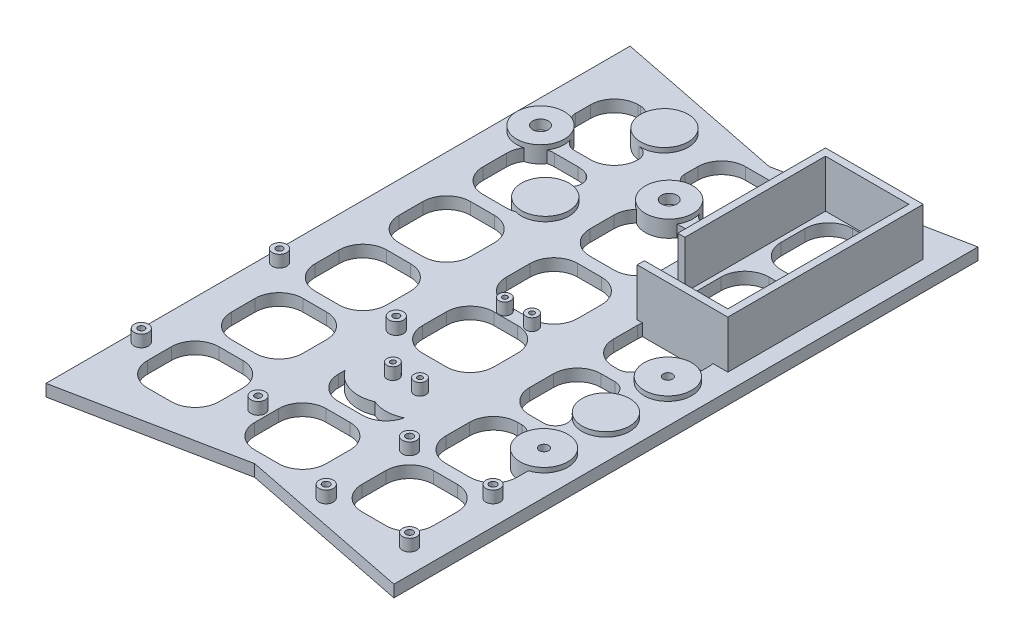
SolidWorks part; units mm, degrees
material "ABS"
ref_plane "Front Plane" through (0, 0, 0) normal (0, 0, 1) x (1, 0, 0)
ref_plane "Top Plane" through (0, 0, 0) normal (0, 1, 0) x (1, 0, 0)
ref_plane "Right Plane" through (0, 0, 0) normal (1, 0, 0) x (0, 0, -1)
ref_axis "X" through (-88.99, 0, 0) along (1, 0, 0)
ref_axis "Y" through (0, 55, 0) along (0, -1, 0)
ref_axis "Z" through (0, 0, -88.99) along (0, 0, 1)
sketch "Sketch1" plane through (0, 0, 0) normal (0, 1, 0) x (1, 0, 0)
  line L0 (-75, 125) -> (0, 110) construction
  line L1 (-75, 125) -> (75, 125) construction
  line L2 (-75, 125) -> (-75, -125) construction
  line L3 (-75, -125) -> (75, -125) construction
  line L4 (75, 125) -> (75, -125) construction
  line L5 (-75, 125) -> (75, -125) construction
  line L6 (-75, -125) -> (75, 125) construction
  line L7 (0, 110) -> (75, 125) construction
  line L8 (-75, 0) -> (75, 0) construction
  line L9 (-75, -125) -> (0, -110) construction
  line L10 (0, -110) -> (75, -125) construction
  line L11 (-73, 122.5604) -> (-73, -122.5604)
  line L12 (-73, -122.5604) -> (0, -107.9604)
  line L13 (0, -107.9604) -> (73, -122.5604)
  line L14 (73, 122.5604) -> (73, -122.5604)
  line L15 (0, 107.9604) -> (73, 122.5604)
  line L16 (-73, 122.5604) -> (0, 107.9604)
  point P0 (0, 0)
  dimension "D1" = 250
  dimension "D2" = 150
  dimension "D3" = 15
  dimension "D4" = 2
extrude "Boss-Extrude1" add sketch "Sketch1" along normal blind 2
sketch "Sketch2" plane through (0, 2, 0) normal (0, 1, 0) x (1, 0, 0)
  line L0 (-73, 122.5604) -> (-73, -122.5604) construction
  line L1 (-50, -102.9604) -> (-40, -102.9604)
  line L2 (-60, -92.9604) -> (-60, -82.9604)
  line L3 (-50, -72.9604) -> (-40, -72.9604)
  line L4 (-30, -92.9604) -> (-30, -82.9604)
  line L5 (-15, -92.9604) -> (-15, -82.9604)
  line L6 (-5, -102.9604) -> (5, -102.9604)
  line L7 (15, -92.9604) -> (15, -82.9604)
  line L8 (-5, -72.9604) -> (5, -72.9604)
  line L9 (30, -92.9604) -> (30, -82.9604)
  line L10 (40, -102.9604) -> (50, -102.9604)
  line L11 (60, -92.9604) -> (60, -82.9604)
  line L12 (40, -72.9604) -> (50, -72.9604)
  line L73 (-60, -57.7762) -> (-60, -47.7762)
  line L74 (-50, -67.7762) -> (-40, -67.7762)
  line L75 (-30, -57.7762) -> (-30, -47.7762)
  line L76 (-50, -37.7762) -> (-40, -37.7762)
  line L77 (-15, -57.7762) -> (-15, -47.7762)
  line L78 (-5, -37.7762) -> (5, -37.7762)
  line L79 (15, -57.7762) -> (15, -47.7762)
  line L80 (-5, -67.7762) -> (5, -67.7762)
  line L81 (30, -57.7762) -> (30, -47.7762)
  line L82 (40, -37.7762) -> (50, -37.7762)
  line L83 (60, -57.7762) -> (60, -47.7762)
  line L84 (40, -67.7762) -> (50, -67.7762)
  line L85 (-60, -22.5921) -> (-60, -12.5921)
  line L86 (-50, -32.5921) -> (-40, -32.5921)
  line L87 (-30, -22.5921) -> (-30, -12.5921)
  line L88 (-50, -2.5921) -> (-40, -2.5921)
  line L89 (-15, -22.5921) -> (-15, -12.5921)
  line L90 (-5, -2.5921) -> (5, -2.5921)
  line L91 (15, -22.5921) -> (15, -12.5921)
  line L92 (-5, -32.5921) -> (5, -32.5921)
  line L93 (30, -22.5921) -> (30, -12.5921)
  line L94 (40, -2.5921) -> (50, -2.5921)
  line L95 (60, -22.5921) -> (60, -12.5921)
  line L96 (40, -32.5921) -> (50, -32.5921)
  line L97 (-60, 12.5921) -> (-60, 22.5921)
  line L98 (-50, 2.5921) -> (-40, 2.5921)
  line L99 (-30, 12.5921) -> (-30, 22.5921)
  line L100 (-50, 32.5921) -> (-40, 32.5921)
  line L101 (-15, 12.5921) -> (-15, 22.5921)
  line L102 (-5, 32.5921) -> (5, 32.5921)
  line L103 (15, 12.5921) -> (15, 22.5921)
  line L104 (-5, 2.5921) -> (5, 2.5921)
  line L105 (30, 12.5921) -> (30, 22.5921)
  line L106 (40, 32.5921) -> (50, 32.5921)
  line L107 (60, 12.5921) -> (60, 22.5921)
  line L108 (40, 2.5921) -> (50, 2.5921)
  line L109 (-60, 47.7762) -> (-60, 57.7762)
  line L110 (-50, 37.7762) -> (-40, 37.7762)
  line L111 (-30, 47.7762) -> (-30, 57.7762)
  line L112 (-50, 67.7762) -> (-40, 67.7762)
  line L113 (-15, 47.7762) -> (-15, 57.7762)
  line L114 (-5, 67.7762) -> (5, 67.7762)
  line L115 (15, 47.7762) -> (15, 57.7762)
  line L116 (-5, 37.7762) -> (5, 37.7762)
  line L117 (30, 47.7762) -> (30, 57.7762)
  line L118 (40, 67.7762) -> (50, 67.7762)
  line L119 (60, 47.7762) -> (60, 57.7762)
  line L120 (40, 37.7762) -> (50, 37.7762)
  line L121 (-60, 82.9604) -> (-60, 92.9604)
  line L122 (-50, 72.9604) -> (-40, 72.9604)
  line L123 (-30, 82.9604) -> (-30, 92.9604)
  line L124 (-50, 102.9604) -> (-40, 102.9604)
  line L125 (-15, 82.9604) -> (-15, 92.9604)
  line L126 (-5, 102.9604) -> (5, 102.9604)
  line L127 (15, 82.9604) -> (15, 92.9604)
  line L128 (-5, 72.9604) -> (5, 72.9604)
  line L129 (30, 82.9604) -> (30, 92.9604)
  line L130 (40, 102.9604) -> (50, 102.9604)
  line L131 (60, 82.9604) -> (60, 92.9604)
  line L132 (40, 72.9604) -> (50, 72.9604)
  arc A0 (-60, -92.9604) -> (-50, -102.9604) centre (-50, -92.9604) ccw
  arc A1 (-40, -102.9604) -> (-30, -92.9604) centre (-40, -92.9604) ccw
  arc A2 (-30, -82.9604) -> (-40, -72.9604) centre (-40, -82.9604) ccw
  arc A3 (-50, -72.9604) -> (-60, -82.9604) centre (-50, -82.9604) ccw
  arc A4 (60, -82.9604) -> (50, -72.9604) centre (50, -82.9604) ccw
  arc A5 (50, -102.9604) -> (60, -92.9604) centre (50, -92.9604) ccw
  arc A6 (40, -102.9604) -> (30, -92.9604) centre (40, -92.9604) cw
  arc A7 (30, -82.9604) -> (40, -72.9604) centre (40, -82.9604) cw
  arc A8 (-15, -82.9604) -> (-5, -72.9604) centre (-5, -82.9604) cw
  arc A9 (-15, -92.9604) -> (-5, -102.9604) centre (-5, -92.9604) ccw
  arc A10 (15, -92.9604) -> (5, -102.9604) centre (5, -92.9604) cw
  arc A11 (15, -82.9604) -> (5, -72.9604) centre (5, -82.9604) ccw
  arc A12 (-50, -37.7762) -> (-60, -47.7762) centre (-50, -47.7762) ccw
  arc A13 (-60, -57.7762) -> (-50, -67.7762) centre (-50, -57.7762) ccw
  arc A14 (-40, -67.7762) -> (-30, -57.7762) centre (-40, -57.7762) ccw
  arc A15 (-30, -47.7762) -> (-40, -37.7762) centre (-40, -47.7762) ccw
  arc A16 (-15, -57.7762) -> (-5, -67.7762) centre (-5, -57.7762) ccw
  arc A17 (-15, -47.7762) -> (-5, -37.7762) centre (-5, -47.7762) cw
  arc A18 (15, -47.7762) -> (5, -37.7762) centre (5, -47.7762) ccw
  arc A19 (15, -57.7762) -> (5, -67.7762) centre (5, -57.7762) cw
  arc A20 (30, -47.7762) -> (40, -37.7762) centre (40, -47.7762) cw
  arc A21 (40, -67.7762) -> (30, -57.7762) centre (40, -57.7762) cw
  arc A22 (60, -47.7762) -> (50, -37.7762) centre (50, -47.7762) ccw
  arc A23 (50, -67.7762) -> (60, -57.7762) centre (50, -57.7762) ccw
  arc A24 (-50, -2.5921) -> (-60, -12.5921) centre (-50, -12.5921) ccw
  arc A25 (-60, -22.5921) -> (-50, -32.5921) centre (-50, -22.5921) ccw
  arc A26 (-40, -32.5921) -> (-30, -22.5921) centre (-40, -22.5921) ccw
  arc A27 (-30, -12.5921) -> (-40, -2.5921) centre (-40, -12.5921) ccw
  arc A28 (-15, -22.5921) -> (-5, -32.5921) centre (-5, -22.5921) ccw
  arc A29 (-15, -12.5921) -> (-5, -2.5921) centre (-5, -12.5921) cw
  arc A30 (15, -12.5921) -> (5, -2.5921) centre (5, -12.5921) ccw
  arc A31 (15, -22.5921) -> (5, -32.5921) centre (5, -22.5921) cw
  arc A32 (30, -12.5921) -> (40, -2.5921) centre (40, -12.5921) cw
  arc A33 (40, -32.5921) -> (30, -22.5921) centre (40, -22.5921) cw
  arc A34 (60, -12.5921) -> (50, -2.5921) centre (50, -12.5921) ccw
  arc A35 (50, -32.5921) -> (60, -22.5921) centre (50, -22.5921) ccw
  arc A36 (-50, 32.5921) -> (-60, 22.5921) centre (-50, 22.5921) ccw
  arc A37 (-60, 12.5921) -> (-50, 2.5921) centre (-50, 12.5921) ccw
  arc A38 (-40, 2.5921) -> (-30, 12.5921) centre (-40, 12.5921) ccw
  arc A39 (-30, 22.5921) -> (-40, 32.5921) centre (-40, 22.5921) ccw
  arc A40 (-15, 12.5921) -> (-5, 2.5921) centre (-5, 12.5921) ccw
  arc A41 (-15, 22.5921) -> (-5, 32.5921) centre (-5, 22.5921) cw
  arc A42 (15, 22.5921) -> (5, 32.5921) centre (5, 22.5921) ccw
  arc A43 (15, 12.5921) -> (5, 2.5921) centre (5, 12.5921) cw
  arc A44 (30, 22.5921) -> (40, 32.5921) centre (40, 22.5921) cw
  arc A45 (40, 2.5921) -> (30, 12.5921) centre (40, 12.5921) cw
  arc A46 (60, 22.5921) -> (50, 32.5921) centre (50, 22.5921) ccw
  arc A47 (50, 2.5921) -> (60, 12.5921) centre (50, 12.5921) ccw
  arc A48 (-50, 67.7762) -> (-60, 57.7762) centre (-50, 57.7762) ccw
  arc A49 (-60, 47.7762) -> (-50, 37.7762) centre (-50, 47.7762) ccw
  arc A50 (-40, 37.7762) -> (-30, 47.7762) centre (-40, 47.7762) ccw
  arc A51 (-30, 57.7762) -> (-40, 67.7762) centre (-40, 57.7762) ccw
  arc A52 (-15, 47.7762) -> (-5, 37.7762) centre (-5, 47.7762) ccw
  arc A53 (-15, 57.7762) -> (-5, 67.7762) centre (-5, 57.7762) cw
  arc A54 (15, 57.7762) -> (5, 67.7762) centre (5, 57.7762) ccw
  arc A55 (15, 47.7762) -> (5, 37.7762) centre (5, 47.7762) cw
  arc A56 (30, 57.7762) -> (40, 67.7762) centre (40, 57.7762) cw
  arc A57 (40, 37.7762) -> (30, 47.7762) centre (40, 47.7762) cw
  arc A58 (60, 57.7762) -> (50, 67.7762) centre (50, 57.7762) ccw
  arc A59 (50, 37.7762) -> (60, 47.7762) centre (50, 47.7762) ccw
  arc A60 (-50, 102.9604) -> (-60, 92.9604) centre (-50, 92.9604) ccw
  arc A61 (-60, 82.9604) -> (-50, 72.9604) centre (-50, 82.9604) ccw
  arc A62 (-40, 72.9604) -> (-30, 82.9604) centre (-40, 82.9604) ccw
  arc A63 (-30, 92.9604) -> (-40, 102.9604) centre (-40, 92.9604) ccw
  arc A64 (-15, 82.9604) -> (-5, 72.9604) centre (-5, 82.9604) ccw
  arc A65 (-15, 92.9604) -> (-5, 102.9604) centre (-5, 92.9604) cw
  arc A66 (15, 92.9604) -> (5, 102.9604) centre (5, 92.9604) ccw
  arc A67 (15, 82.9604) -> (5, 72.9604) centre (5, 82.9604) cw
  arc A68 (30, 92.9604) -> (40, 102.9604) centre (40, 92.9604) cw
  arc A69 (40, 72.9604) -> (30, 82.9604) centre (40, 82.9604) cw
  arc A70 (60, 92.9604) -> (50, 102.9604) centre (50, 92.9604) ccw
  arc A71 (50, 72.9604) -> (60, 82.9604) centre (50, 82.9604) ccw
  point P81 (-30, -102.9604)
  point P84 (-30, -72.9604)
  point P87 (-60, -72.9604)
  dimension "D9" = 10
  dimension "D7" = 10
  dimension "D1" = 30
  dimension "D2" = 30
  dimension "D3" = 13
  dimension "D4" = 5
  dimension "D6" = 15
  dimension "D8" = 6
  dimension "D10" = 5
  dimension "D5" = 3
extrude "Cut-Extrude1" cut sketch "Sketch2" against normal through all
sketch "Sketch3" plane through (0, 2, 0) normal (0, 1, 0) x (1, 0, 0)
  line L1 (-73, 122.5604) -> (-73, -122.5604) construction
  circle A0 centre (-68, -29.5604) radius 3
  circle A1 centre (-19, -29.5604) radius 3
  circle A2 centre (-68, -87.5604) radius 3
  circle A3 centre (-19, -87.5604) radius 3
  dimension "D1" = 6
  dimension "D2" = 49
  dimension "D3" = 58
  dimension "D4" = 5
  dimension "D5" = 35
extrude "Boss-Extrude2" add sketch "Sketch3" along normal blind 5 and the other way through all
sketch "Sketch4" plane through (0, 7, 0) normal (0, 1, 0) x (1, 0, 0)
  circle A1 centre (-19, -87.5604) radius 1.35
  circle A2 centre (-68, -87.5604) radius 1.35
  circle A3 centre (-68, -29.5604) radius 1.35
  circle A4 centre (-19, -29.5604) radius 1.35
  dimension "D1" = 2.7
extrude "Cut-Extrude2" cut sketch "Sketch4" against normal through all
sketch "Sketch5" plane through (0, 2, 0) normal (0, 1, 0) x (1, 0, 0)
  line L0 (30, -87.9604) -> (60, -87.9604) construction
  line L1 (30, -82.9604) -> (30, -92.9604) construction
  line L2 (60, -92.9604) -> (60, -82.9604) construction
  circle A0 centre (27.5, -70.4604) radius 3
  circle A2 centre (62.5, -70.4604) radius 3
  circle A4 centre (62.5, -105.4604) radius 3
  circle A6 centre (27.5, -105.4604) radius 3
  circle A9 centre (45, -87.9604) radius 24.7487 construction
  dimension "D2" = 6
  dimension "D3" = 35
  dimension "D4" = 35
extrude "Boss-Extrude3" add sketch "Sketch5" along normal blind 5
sketch "Sketch6" plane through (0, 7, 0) normal (0, 1, 0) x (1, 0, 0)
  circle A0 centre (27.5, -70.4604) radius 1.5
  circle A1 centre (62.5, -70.4604) radius 1.5
  circle A2 centre (62.5, -105.4604) radius 1.5
  circle A3 centre (27.5, -105.4604) radius 1.5
  dimension "D1" = 3
extrude "Cut-Extrude3" cut sketch "Sketch6" against normal through all
sketch "Sketch7" plane through (0, 2, 0) normal (0, 1, 0) x (1, 0, 0)
  line L0 (73, -122.5604) -> (73, 122.5604) construction
  line L1 (30, -17.5921) -> (73, -17.5921) construction
  line L2 (30, -12.5921) -> (30, -22.5921) construction
  line L3 (57, 8.4079) -> (57, -43.5921) construction
  circle A0 centre (57, -43.5921) radius 10
  circle A1 centre (57, 8.4079) radius 10
  circle A2 centre (57, -17.5921) radius 10
  point P6 (51.5, -17.5921)
  point P13 (57, -17.5921)
  dimension "D1" = 20
  dimension "D2" = 16
  dimension "D3" = 52
extrude "Boss-Extrude4" add sketch "Sketch7" along normal blind 2 and the other way through all
sketch "Sketch8" plane through (0, 4, 0) normal (0, 1, 0) x (1, 0, 0)
  circle A0 centre (57, 8.4079) radius 1.95
  circle A1 centre (57, -43.5921) radius 1.95
  dimension "D1" = 3.9
extrude "Cut-Extrude4" cut sketch "Sketch8" against normal through all
sketch "Sketch9" plane through (0, 2, 0) normal (0, 1, 0) x (1, 0, 0)
  line L0 (73, 0) -> (-73, 0) construction
  line L1 (73, -122.5604) -> (73, 122.5604) construction
  line L2 (-73, 122.5604) -> (-73, -122.5604) construction
  circle A0 centre (-3, 0) radius 2.5
  circle A1 centre (-3, -47) radius 2.5
  circle A2 centre (8.4, -47) radius 2.5
  circle A3 centre (8.4, 0) radius 2.5
  dimension "D1" = 5
  dimension "D4" = 70
  dimension "D2" = 11.4
  dimension "D3" = 47
extrude "Boss-Extrude5" add sketch "Sketch9" along normal blind 5
sketch "Sketch16" plane through (0, 2, 0) normal (0, -1, 0) x (1, 0, 0)
  line L0 (-5, 32.5921) -> (5, 32.5921) construction
  circle A0 centre (8.4, 47) radius 14.4079
  circle A1 centre (-3, 47) radius 14.4079
  circle M3 centre (8.4, 47) radius 2.5
extrude "Boss-Extrude10" add sketch "Sketch16" along normal up to surface (2 mm away) contours A0 A1 | A0 A1 M3 | M3 | A1 A0 region at (14.3268, 2, 47) region at (2.3422, 2, 47) region at (-8.9268, 2, 47) region at (8.4, 2, 47) up to face at (57, 0, -6.4579)
sketch "Sketch10" plane through (0, 7, 0) normal (0, 1, 0) x (1, 0, 0)
  circle A0 centre (8.4, 0) radius 1.05
  circle A1 centre (8.4, -47) radius 1.05
  circle A2 centre (-3, -47) radius 1.05
  circle A3 centre (-3, 0) radius 1.05
  dimension "D1" = 2.1
extrude "Cut-Extrude5" cut sketch "Sketch10" against normal through all
sketch "Sketch11" plane through (0, 2, 0) normal (0, 1, 0) x (1, 0, 0)
  line L0 (-73, 122.5604) -> (-73, -122.5604) construction
  line L1 (-34, 97.9604) -> (-34, 47.9604) construction
  line L2 (-61, 72.9604) -> (-7, 72.9604) construction
  circle A3 centre (-7, 72.9604) radius 10
  circle A4 centre (-61, 72.9604) radius 10
  circle A5 centre (-34, 97.9604) radius 10
  circle A6 centre (-34, 47.9604) radius 10
  point P11 (-34, 72.9604)
  dimension "D1" = 20
  dimension "D2" = 54
  dimension "D3" = 35
  dimension "D4" = 12
  dimension "D5" = 50
extrude "Boss-Extrude6" add sketch "Sketch11" along normal blind 2 and the other way through all
sketch "Sketch12" plane through (0, 4, 0) normal (0, 1, 0) x (1, 0, 0)
  circle A0 centre (-61, 72.9604) radius 3.25
  circle A1 centre (-7, 72.9604) radius 3.25
  dimension "D1" = 6.5
extrude "Cut-Extrude6" cut sketch "Sketch12" against normal through all
sketch "Sketch13" plane through (0, 2, 0) normal (0, 1, 0) x (1, 0, 0)
  line L0 (28, 24.5604) -> (66, 24.5604)
  line L1 (66, 24.5604) -> (66, 106.5604)
  line L2 (66, 106.5604) -> (25, 106.5604)
  line L3 (25, 106.5604) -> (25, 44.5604)
  line L4 (25, 44.5604) -> (28, 44.5604)
  line L5 (28, 44.5604) -> (28, 103.5604)
  line L6 (28, 103.5604) -> (63, 103.5604)
  line L7 (63, 103.5604) -> (63, 27.5604)
  line L8 (63, 27.5604) -> (28, 27.5604)
  line L9 (28, 27.5604) -> (28, 24.5604)
  line L10 (73, -122.5604) -> (73, 122.5604) construction
  dimension "D1" = 62
  dimension "D2" = 3
  dimension "D3" = 3
  dimension "D4" = 3
  dimension "D5" = 3
  dimension "D6" = 35
  dimension "D7" = 76
  dimension "D8" = 16
  dimension "D9" = 7
extrude "Boss-Extrude7" add sketch "Sketch13" along normal blind 20 and the other way through all
fillet "Fillet2" radius 5 11 edges at (48.8651, 1, -2.5921) (48.8651, 1, 37.7762) (58.7473, 1, 27.4382) (58.7473, 1, 7.7459) (-30, 1, -57.1255) (-14.4353, 1, -79.6474) (3, 1, -72.9604) (-59.9999, 1, -82.9103) (-51.0001, 1, -73.0105) (-42.6603, 1, -102.9604) (-30, 1, -88.7952)
sketch "Sketch15" plane through (0, 0, 0) normal (0, -1, 0) x (1, 0, 0)
  line L0 (0, 107.9604) -> (73, 122.5604) construction
  line L1 (-73, 122.5604) -> (0, 107.9604) construction
  line L2 (73, 122.5604) -> (73, -122.5604) construction
  line L3 (73, -122.5604) -> (0, -107.9604) construction
  line L4 (0, -107.9604) -> (-73, -122.5604) construction
  line L5 (-73, -122.5604) -> (-73, 122.5604) construction
  line L6 (0, 107.9604) -> (73, 122.5604)
  line L7 (-73, 122.5604) -> (0, 107.9604)
  line L8 (73, 122.5604) -> (73, -122.5604)
  line L9 (73, -122.5604) -> (0, -107.9604)
  line L10 (0, -107.9604) -> (-73, -122.5604)
  line L11 (-73, -122.5604) -> (-73, 122.5604)
  line L12 (0, 104.901) -> (70, 118.901)
  line L13 (70, 118.901) -> (70, -118.901)
  line L14 (70, -118.901) -> (0, -104.901)
  line L15 (0, -104.901) -> (-70, -118.901)
  line L16 (-70, -118.901) -> (-70, 118.901)
  line L17 (-70, 118.901) -> (0, 104.901)
  dimension "D1" = 3
extrude "Boss-Extrude9" add sketch "Sketch15" along normal blind 3
sketch "Sketch17" plane through (0, 0, 0) normal (0, -1, 0) x (1, 0, 0)
  line L4 (-40, 72.9604) -> (-50, 72.9604) construction
  line L5 (-30, 92.9604) -> (-30, 82.9604) construction
  line L6 (-50, 102.9604) -> (-40, 102.9604) construction
  line L7 (-60, 82.9604) -> (-60, 92.9604) construction
  line L8 (-40, 37.7762) -> (-50, 37.7762) construction
  line L9 (-30, 57.7762) -> (-30, 47.7762) construction
  line L10 (-50, 67.7762) -> (-40, 67.7762) construction
  line L11 (-60, 47.7762) -> (-60, 57.7762) construction
  line L12 (-15, 54.9742) -> (-15, 57.7762) construction
  line L13 (-5, 67.7762) -> (5, 67.7762) construction
  line L14 (5, 2.5921) -> (-5, 2.5921) construction
  line L15 (15, 22.5921) -> (15, 12.5921) construction
  line L16 (-5, 32.5921) -> (5, 32.5921) construction
  line L17 (-15, 12.5921) -> (-15, 22.5921) construction
  line L18 (-60, 12.5921) -> (-60, 22.5921) construction
  line L19 (-40, 2.5921) -> (-50, 2.5921) construction
  line L20 (-30, 22.5921) -> (-30, 12.5921) construction
  line L21 (-50, 32.5921) -> (-40, 32.5921) construction
  line L94 (-40, 72.9604) -> (-50, 72.9604)
  line L95 (-30, 92.9604) -> (-30, 82.9604)
  line L96 (-50, 102.9604) -> (-40, 102.9604)
  line L97 (-60, 82.9604) -> (-60, 92.9604)
  line L98 (-40, 37.7762) -> (-50, 37.7762)
  line L99 (-30, 57.7762) -> (-30, 47.7762)
  line L100 (-50, 67.7762) -> (-40, 67.7762)
  line L101 (-60, 47.7762) -> (-60, 57.7762)
  line L102 (-15, 54.9742) -> (-15, 57.7762)
  line L103 (-5, 67.7762) -> (5, 67.7762)
  line L104 (5, 2.5921) -> (-5, 2.5921)
  line L105 (15, 22.5921) -> (15, 12.5921)
  line L106 (-5, 32.5921) -> (5, 32.5921)
  line L107 (-15, 12.5921) -> (-15, 22.5921)
  line L108 (-60, 12.5921) -> (-60, 22.5921)
  line L109 (-40, 2.5921) -> (-50, 2.5921)
  line L110 (-30, 22.5921) -> (-30, 12.5921)
  line L111 (-50, 32.5921) -> (-40, 32.5921)
  line L112 (60, 57.7762) -> (60, 53.1315) construction
  line L113 (42.0222, 37.7762) -> (40, 37.7762) construction
  line L114 (30, 47.7762) -> (30, 57.7762) construction
  line L115 (40, 67.7762) -> (50, 67.7762) construction
  line L116 (60, 92.9604) -> (60, 82.9604) construction
  line L117 (50, 72.9604) -> (40, 72.9604) construction
  line L118 (30, 82.9604) -> (30, 92.9604) construction
  line L119 (40, 102.9604) -> (50, 102.9604) construction
  line L120 (5, 72.9604) -> (-5, 72.9604) construction
  line L121 (15, 92.9604) -> (15, 82.9604) construction
  line L122 (-5, 102.9604) -> (5, 102.9604) construction
  line L123 (-15, 82.9604) -> (-15, 92.9604) construction
  line L124 (60, 57.7762) -> (60, 53.1315)
  line L125 (42.0222, 37.7762) -> (40, 37.7762)
  line L126 (30, 47.7762) -> (30, 57.7762)
  line L127 (40, 67.7762) -> (50, 67.7762)
  line L128 (60, 92.9604) -> (60, 82.9604)
  line L129 (50, 72.9604) -> (40, 72.9604)
  line L130 (30, 82.9604) -> (30, 92.9604)
  line L131 (40, 102.9604) -> (50, 102.9604)
  line L132 (5, 72.9604) -> (-5, 72.9604)
  line L133 (15, 92.9604) -> (15, 82.9604)
  line L134 (-5, 102.9604) -> (5, 102.9604)
  line L135 (-15, 82.9604) -> (-15, 92.9604)
  line L136 (40, -2.5921) -> (42.0222, -2.5921) construction
  line L137 (30, -22.5921) -> (30, -12.5921) construction
  line L138 (60, -17.9473) -> (60, -22.5921) construction
  line L139 (30.1956, -24.5604) -> (59.8044, -24.5604) construction
  line L140 (58.6785, -27.5604) -> (31.3215, -27.5604) construction
  line L141 (50, -32.5921) -> (40, -32.5921) construction
  line L142 (40, -2.5921) -> (42.0222, -2.5921)
  line L143 (30, -22.5921) -> (30, -12.5921)
  line L144 (60, -17.9473) -> (60, -22.5921)
  line L145 (30.1956, -24.5604) -> (59.8044, -24.5604)
  line L146 (58.6785, -27.5604) -> (31.3215, -27.5604)
  line L147 (50, -32.5921) -> (40, -32.5921)
  line L148 (5, -32.5921) -> (-5, -32.5921) construction
  line L149 (-5, -2.5921) -> (5, -2.5921) construction
  line L150 (-15, -22.5921) -> (-15, -12.5921) construction
  line L151 (15, -12.5921) -> (15, -22.5921) construction
  line L152 (30, 12.5921) -> (30, 22.5921) construction
  line L153 (45.8197, 2.5921) -> (40, 2.5921) construction
  line L154 (40, 32.5921) -> (45.8197, 32.5921) construction
  line L155 (5, -32.5921) -> (-5, -32.5921)
  line L156 (-5, -2.5921) -> (5, -2.5921)
  line L157 (-15, -22.5921) -> (-15, -12.5921)
  line L158 (15, -12.5921) -> (15, -22.5921)
  line L159 (30, 12.5921) -> (30, 22.5921)
  line L160 (45.8197, 2.5921) -> (40, 2.5921)
  line L161 (40, 32.5921) -> (45.8197, 32.5921)
  line L162 (-60, -57.7762) -> (-60, -47.7762) construction
  line L163 (-40, -67.7762) -> (-50, -67.7762) construction
  line L164 (-50, -37.7762) -> (-40, -37.7762) construction
  line L165 (-40, -32.5921) -> (-50, -32.5921) construction
  line L166 (-30, -12.5921) -> (-30, -22.5921) construction
  line L167 (-50, -2.5921) -> (-40, -2.5921) construction
  line L168 (-60, -22.5921) -> (-60, -12.5921) construction
  line L169 (-60, -57.7762) -> (-60, -47.7762)
  line L170 (-40, -67.7762) -> (-50, -67.7762)
  line L171 (-50, -37.7762) -> (-40, -37.7762)
  line L172 (-40, -32.5921) -> (-50, -32.5921)
  line L173 (-30, -12.5921) -> (-30, -22.5921)
  line L174 (-50, -2.5921) -> (-40, -2.5921)
  line L175 (-60, -22.5921) -> (-60, -12.5921)
  line L176 (60, -82.9604) -> (60, -92.9604) construction
  line L177 (50, -102.9604) -> (40, -102.9604) construction
  line L178 (40, -72.9604) -> (50, -72.9604) construction
  line L179 (30, -92.9604) -> (30, -82.9604) construction
  line L180 (15, -82.9604) -> (15, -92.9604) construction
  line L181 (5, -102.9604) -> (-5, -102.9604) construction
  line L182 (-15, -92.9604) -> (-15, -87.6573) construction
  line L186 (60, -82.9604) -> (60, -92.9604)
  line L187 (50, -102.9604) -> (40, -102.9604)
  line L188 (40, -72.9604) -> (50, -72.9604)
  line L189 (30, -92.9604) -> (30, -82.9604)
  line L190 (15, -82.9604) -> (15, -92.9604)
  line L191 (5, -102.9604) -> (-5, -102.9604)
  line L192 (-15, -92.9604) -> (-15, -87.6573)
  line L196 (50, -67.7762) -> (40, -67.7762) construction
  line L197 (60, -47.7762) -> (60, -57.7762) construction
  line L198 (40, -37.7762) -> (50, -37.7762) construction
  line L199 (30, -57.7762) -> (30, -47.7762) construction
  line L200 (5, -67.7762) -> (1.5513, -67.7762) construction
  line L201 (15, -47.7762) -> (15, -57.7762) construction
  line L202 (-5, -37.7762) -> (5, -37.7762) construction
  line L203 (-15, -57.7762) -> (-15, -47.7762) construction
  line L204 (50, -67.7762) -> (40, -67.7762)
  line L205 (60, -47.7762) -> (60, -57.7762)
  line L206 (40, -37.7762) -> (50, -37.7762)
  line L207 (30, -57.7762) -> (30, -47.7762)
  line L208 (5, -67.7762) -> (1.5513, -67.7762)
  line L209 (15, -47.7762) -> (15, -57.7762)
  line L210 (-5, -37.7762) -> (5, -37.7762)
  line L211 (-15, -57.7762) -> (-15, -47.7762)
  line L212 (-30, -82.9604) -> (-30, -82.9938) construction
  line L213 (-46.8579, -72.9604) -> (-40, -72.9604) construction
  line L214 (-60, -92.9604) -> (-60, -86.7081) construction
  line L215 (-49, -102.9604) -> (-50, -102.9604) construction
  line L216 (-30, -82.9604) -> (-30, -82.9938)
  line L217 (-46.8579, -72.9604) -> (-40, -72.9604)
  line L218 (-60, -92.9604) -> (-60, -86.7081)
  line L219 (-49, -102.9604) -> (-50, -102.9604)
  line L220 (-49, -104.9604) -> (-50, -104.9604)
  line L221 (-62, -92.9604) -> (-62, -86.7081)
  line L222 (-46.8579, -70.9604) -> (-40, -70.9604)
  line L223 (-28, -82.9604) -> (-28, -82.9938)
  line L224 (-62, -57.7762) -> (-62, -47.7762)
  line L225 (-40, -69.7762) -> (-50, -69.7762)
  line L226 (-50, -35.7762) -> (-40, -35.7762)
  line L227 (5, -69.7762) -> (0.339, -69.7762)
  line L228 (-17, -57.7762) -> (-17, -47.7762)
  line L229 (-5, -35.7762) -> (5, -35.7762)
  line L230 (17, -47.7762) -> (17, -57.7762)
  line L231 (17, -82.9604) -> (17, -92.9604)
  line L232 (-17, -92.9604) -> (-17, -87.6573)
  line L233 (5, -104.9604) -> (-5, -104.9604)
  line L234 (40, -70.9604) -> (50, -70.9604)
  line L235 (28, -92.9604) -> (28, -82.9604)
  line L236 (50, -104.9604) -> (40, -104.9604)
  line L237 (62, -82.9604) -> (62, -92.9604)
  line L238 (50, -69.7762) -> (40, -69.7762)
  line L239 (28, -57.7762) -> (28, -47.7762)
  line L240 (40, -35.7762) -> (50, -35.7762)
  line L241 (62, -47.7762) -> (62, -57.7762)
  line L242 (40, -0.5921) -> (42.0222, -0.5921)
  line L243 (62, -14.6529) -> (62, -22.5921)
  line L245 (28, -22.5921) -> (28, -12.5921)
  line L247 (50, -34.5921) -> (40, -34.5921)
  line L252 (-40, -34.5921) -> (-50, -34.5921)
  line L253 (-28, -12.5921) -> (-28, -22.5921)
  line L254 (-50, -0.5921) -> (-40, -0.5921)
  line L255 (-62, -22.5921) -> (-62, -12.5921)
  line L256 (-62, 12.5921) -> (-62, 22.5921)
  line L257 (-50, 34.5921) -> (-40, 34.5921)
  line L258 (-28, 22.5921) -> (-28, 12.5921)
  line L259 (-40, 0.5921) -> (-50, 0.5921)
  line L264 (28, 12.5921) -> (28, 22.5921)
  line L265 (40, 34.5921) -> (45.8197, 34.5921)
  line L266 (45.8197, 0.5921) -> (40, 0.5921)
  line L267 (62, 57.7762) -> (62, 49.8371)
  line L268 (42.0222, 35.7762) -> (40, 35.7762)
  line L269 (28, 47.7762) -> (28, 57.7762)
  line L270 (40, 69.7762) -> (50, 69.7762)
  line L271 (-40, 35.7762) -> (-50, 35.7762)
  line L272 (-28, 57.7762) -> (-28, 47.7762)
  line L273 (-50, 69.7762) -> (-40, 69.7762)
  line L274 (-62, 47.7762) -> (-62, 57.7762)
  line L275 (5, 70.9604) -> (-5, 70.9604)
  line L276 (17, 92.9604) -> (17, 82.9604)
  line L277 (-5, 104.9604) -> (5, 104.9604)
  line L278 (-17, 82.9604) -> (-17, 92.9604)
  line L279 (40, 104.9604) -> (50, 104.9604)
  line L280 (28, 82.9604) -> (28, 92.9604)
  line L281 (50, 70.9604) -> (40, 70.9604)
  line L282 (62, 92.9604) -> (62, 82.9604)
  line L283 (-40, 70.9604) -> (-50, 70.9604)
  line L284 (-28, 92.9604) -> (-28, 82.9604)
  line L285 (-50, 104.9604) -> (-40, 104.9604)
  line L286 (-62, 82.9604) -> (-62, 92.9604)
  line L287 (-16, 50.2821) -> (-16, 57.7762)
  line L288 (-5, 68.7762) -> (5, 68.7762)
  line L289 (5, 1.5921) -> (-5, 1.5921)
  line L290 (16, 22.5921) -> (16, 12.5921)
  line L291 (-5, 33.5921) -> (5, 33.5921)
  line L292 (-16, 12.5921) -> (-16, 22.5921)
  line L293 (5, -33.5921) -> (-5, -33.5921)
  line L294 (28.6751, -26.5604) -> (61.3249, -26.5604) construction
  line L295 (61.6271, -25.5604) -> (28.3729, -25.5604) construction
  line L296 (-16, -22.5921) -> (-16, -12.5921)
  line L297 (-5, -1.5921) -> (5, -1.5921)
  line L298 (16, -12.5921) -> (16, -22.5921)
  arc A2 (-60, 82.9604) -> (-50, 72.9604) centre (-50, 82.9604) ccw construction
  arc A3 (-40, 72.9604) -> (-30, 82.9604) centre (-40, 82.9604) ccw construction
  arc A4 (-30, 92.9604) -> (-40, 102.9604) centre (-40, 92.9604) ccw construction
  arc A5 (-50, 102.9604) -> (-60, 92.9604) centre (-50, 92.9604) ccw construction
  arc A6 (-60, 47.7762) -> (-50, 37.7762) centre (-50, 47.7762) ccw construction
  arc A7 (-40, 37.7762) -> (-30, 47.7762) centre (-40, 47.7762) ccw construction
  arc A8 (-30, 57.7762) -> (-40, 67.7762) centre (-40, 57.7762) ccw construction
  arc A9 (-50, 67.7762) -> (-60, 57.7762) centre (-50, 57.7762) ccw construction
  arc A10 (2.7, 60.2325) -> (-15, 54.9742) centre (-3, 47) ccw construction
  arc A11 (14.7664, 59.9251) -> (2.7, 60.2325) centre (8.4, 47) ccw construction
  arc A12 (14.7664, 59.9251) -> (5, 67.7762) centre (5, 57.7762) ccw construction
  arc A13 (-5, 67.7762) -> (-15, 57.7762) centre (-5, 57.7762) ccw construction
  arc A14 (-15, 12.5921) -> (-5, 2.5921) centre (-5, 12.5921) ccw construction
  arc A15 (5, 2.5921) -> (15, 12.5921) centre (5, 12.5921) ccw construction
  arc A16 (15, 22.5921) -> (5, 32.5921) centre (5, 22.5921) ccw construction
  arc A17 (-5, 32.5921) -> (-15, 22.5921) centre (-5, 22.5921) ccw construction
  arc A18 (-60, 12.5921) -> (-50, 2.5921) centre (-50, 12.5921) ccw construction
  arc A19 (-40, 2.5921) -> (-30, 12.5921) centre (-40, 12.5921) ccw construction
  arc A20 (-30, 22.5921) -> (-40, 32.5921) centre (-40, 22.5921) ccw construction
  arc A21 (-50, 32.5921) -> (-60, 22.5921) centre (-50, 22.5921) ccw construction
  arc A102 (-60, 82.9604) -> (-50, 72.9604) centre (-50, 82.9604) ccw
  arc A103 (-40, 72.9604) -> (-30, 82.9604) centre (-40, 82.9604) ccw
  arc A104 (-30, 92.9604) -> (-40, 102.9604) centre (-40, 92.9604) ccw
  arc A105 (-50, 102.9604) -> (-60, 92.9604) centre (-50, 92.9604) ccw
  arc A106 (-60, 47.7762) -> (-50, 37.7762) centre (-50, 47.7762) ccw
  arc A107 (-40, 37.7762) -> (-30, 47.7762) centre (-40, 47.7762) ccw
  arc A108 (-30, 57.7762) -> (-40, 67.7762) centre (-40, 57.7762) ccw
  arc A109 (-50, 67.7762) -> (-60, 57.7762) centre (-50, 57.7762) ccw
  arc A110 (2.7, 60.2325) -> (-15, 54.9742) centre (-3, 47) ccw
  arc A111 (14.7664, 59.9251) -> (2.7, 60.2325) centre (8.4, 47) ccw
  arc A112 (14.7664, 59.9251) -> (5, 67.7762) centre (5, 57.7762) ccw
  arc A113 (-5, 67.7762) -> (-15, 57.7762) centre (-5, 57.7762) ccw
  arc A114 (-15, 12.5921) -> (-5, 2.5921) centre (-5, 12.5921) ccw
  arc A115 (5, 2.5921) -> (15, 12.5921) centre (5, 12.5921) ccw
  arc A116 (15, 22.5921) -> (5, 32.5921) centre (5, 22.5921) ccw
  arc A117 (-5, 32.5921) -> (-15, 22.5921) centre (-5, 22.5921) ccw
  arc A118 (-60, 12.5921) -> (-50, 2.5921) centre (-50, 12.5921) ccw
  arc A119 (-40, 2.5921) -> (-30, 12.5921) centre (-40, 12.5921) ccw
  arc A120 (-30, 22.5921) -> (-40, 32.5921) centre (-40, 22.5921) ccw
  arc A121 (-50, 32.5921) -> (-60, 22.5921) centre (-50, 22.5921) ccw
  arc A122 (60, 57.7762) -> (50, 67.7762) centre (50, 57.7762) ccw construction
  arc A123 (60, 53.1315) -> (47.0148, 43.0482) centre (57, 43.5921) ccw construction
  arc A124 (42.0222, 37.7762) -> (47.0148, 43.0482) centre (42.0222, 42.7762) ccw construction
  arc A125 (30, 47.7762) -> (40, 37.7762) centre (40, 47.7762) ccw construction
  arc A126 (40, 67.7762) -> (30, 57.7762) centre (40, 57.7762) ccw construction
  arc A127 (60, 92.9604) -> (50, 102.9604) centre (50, 92.9604) ccw construction
  arc A128 (50, 72.9604) -> (60, 82.9604) centre (50, 82.9604) ccw construction
  arc A129 (30, 82.9604) -> (40, 72.9604) centre (40, 82.9604) ccw construction
  arc A130 (40, 102.9604) -> (30, 92.9604) centre (40, 92.9604) ccw construction
  arc A131 (-15, 82.9604) -> (-5, 72.9604) centre (-5, 82.9604) ccw construction
  arc A132 (5, 72.9604) -> (15, 82.9604) centre (5, 82.9604) ccw construction
  arc A133 (15, 92.9604) -> (5, 102.9604) centre (5, 92.9604) ccw construction
  arc A134 (-5, 102.9604) -> (-15, 92.9604) centre (-5, 92.9604) ccw construction
  arc A135 (60, 57.7762) -> (50, 67.7762) centre (50, 57.7762) ccw
  arc A136 (60, 53.1315) -> (47.0148, 43.0482) centre (57, 43.5921) ccw
  arc A137 (42.0222, 37.7762) -> (47.0148, 43.0482) centre (42.0222, 42.7762) ccw
  arc A138 (30, 47.7762) -> (40, 37.7762) centre (40, 47.7762) ccw
  arc A139 (40, 67.7762) -> (30, 57.7762) centre (40, 57.7762) ccw
  arc A140 (60, 92.9604) -> (50, 102.9604) centre (50, 92.9604) ccw
  arc A141 (50, 72.9604) -> (60, 82.9604) centre (50, 82.9604) ccw
  arc A142 (30, 82.9604) -> (40, 72.9604) centre (40, 82.9604) ccw
  arc A143 (40, 102.9604) -> (30, 92.9604) centre (40, 92.9604) ccw
  arc A144 (-15, 82.9604) -> (-5, 72.9604) centre (-5, 82.9604) ccw
  arc A145 (5, 72.9604) -> (15, 82.9604) centre (5, 82.9604) ccw
  arc A146 (15, 92.9604) -> (5, 102.9604) centre (5, 92.9604) ccw
  arc A147 (-5, 102.9604) -> (-15, 92.9604) centre (-5, 92.9604) ccw
  arc A148 (47.0148, -7.864) -> (42.0222, -2.5921) centre (42.0222, -7.5921) ccw construction
  arc A149 (40, -2.5921) -> (30, -12.5921) centre (40, -12.5921) ccw construction
  arc A150 (30, -22.5921) -> (30.1956, -24.5604) centre (40, -22.5921) ccw construction
  arc A151 (47.0148, -7.864) -> (60, -17.9473) centre (57, -8.4079) ccw construction
  arc A152 (59.8044, -24.5604) -> (60, -22.5921) centre (50, -22.5921) ccw construction
  arc A153 (50, -32.5921) -> (58.6785, -27.5604) centre (50, -22.5921) ccw construction
  arc A154 (31.3215, -27.5604) -> (40, -32.5921) centre (40, -22.5921) ccw construction
  arc A155 (47.0148, -7.864) -> (42.0222, -2.5921) centre (42.0222, -7.5921) ccw
  arc A156 (40, -2.5921) -> (30, -12.5921) centre (40, -12.5921) ccw
  arc A157 (30, -22.5921) -> (30.1956, -24.5604) centre (40, -22.5921) ccw
  arc A158 (47.0148, -7.864) -> (60, -17.9473) centre (57, -8.4079) ccw
  arc A159 (59.8044, -24.5604) -> (60, -22.5921) centre (50, -22.5921) ccw
  arc A160 (50, -32.5921) -> (58.6785, -27.5604) centre (50, -22.5921) ccw
  arc A161 (31.3215, -27.5604) -> (40, -32.5921) centre (40, -22.5921) ccw
  arc A162 (5, -32.5921) -> (15, -22.5921) centre (5, -22.5921) ccw construction
  arc A163 (15, -12.5921) -> (5, -2.5921) centre (5, -12.5921) ccw construction
  arc A164 (-5, -2.5921) -> (-15, -12.5921) centre (-5, -12.5921) ccw construction
  arc A165 (-15, -22.5921) -> (-5, -32.5921) centre (-5, -22.5921) ccw construction
  arc A166 (30, 12.5921) -> (40, 2.5921) centre (40, 12.5921) ccw construction
  arc A167 (45.8197, 2.5921) -> (49.5464, 10.9254) centre (45.8197, 7.5921) ccw construction
  arc A168 (49.5464, 24.2587) -> (49.5464, 10.9254) centre (57, 17.5921) ccw construction
  arc A169 (49.5464, 24.2587) -> (45.8197, 32.5921) centre (45.8197, 27.5921) ccw construction
  arc A170 (40, 32.5921) -> (30, 22.5921) centre (40, 22.5921) ccw construction
  arc A171 (5, -32.5921) -> (15, -22.5921) centre (5, -22.5921) ccw
  arc A172 (15, -12.5921) -> (5, -2.5921) centre (5, -12.5921) ccw
  arc A173 (-5, -2.5921) -> (-15, -12.5921) centre (-5, -12.5921) ccw
  arc A174 (-15, -22.5921) -> (-5, -32.5921) centre (-5, -22.5921) ccw
  arc A175 (30, 12.5921) -> (40, 2.5921) centre (40, 12.5921) ccw
  arc A176 (45.8197, 2.5921) -> (49.5464, 10.9254) centre (45.8197, 7.5921) ccw
  arc A177 (49.5464, 24.2587) -> (49.5464, 10.9254) centre (57, 17.5921) ccw
  arc A178 (49.5464, 24.2587) -> (45.8197, 32.5921) centre (45.8197, 27.5921) ccw
  arc A179 (40, 32.5921) -> (30, 22.5921) centre (40, 22.5921) ccw
  arc A180 (-50, -37.7762) -> (-60, -47.7762) centre (-50, -47.7762) ccw construction
  arc A181 (-60, -57.7762) -> (-58.3182, -63.3267) centre (-50, -57.7762) ccw construction
  arc A182 (-52.6818, -67.4099) -> (-50, -67.7762) centre (-50, -57.7762) ccw construction
  arc A183 (-52.6818, -67.4099) -> (-58.3182, -63.3267) centre (-61, -72.9604) ccw construction
  arc A184 (-40, -67.7762) -> (-36.1656, -67.0119) centre (-40, -57.7762) ccw construction
  arc A185 (-36.1656, -67.0119) -> (-36.7219, -57.5828) centre (-38.0828, -62.3941) ccw construction
  arc A186 (-36.7074, -38.3339) -> (-36.7219, -57.5828) centre (-34, -47.9604) ccw construction
  arc A187 (-36.7074, -38.3339) -> (-40, -37.7762) centre (-40, -47.7762) ccw construction
  arc A188 (-60, -22.5921) -> (-50, -32.5921) centre (-50, -22.5921) ccw construction
  arc A189 (-40, -32.5921) -> (-30, -22.5921) centre (-40, -22.5921) ccw construction
  arc A190 (-30, -12.5921) -> (-40, -2.5921) centre (-40, -12.5921) ccw construction
  arc A191 (-50, -2.5921) -> (-60, -12.5921) centre (-50, -12.5921) ccw construction
  arc A192 (-50, -37.7762) -> (-60, -47.7762) centre (-50, -47.7762) ccw
  arc A193 (-60, -57.7762) -> (-58.3182, -63.3267) centre (-50, -57.7762) ccw
  arc A194 (-52.6818, -67.4099) -> (-50, -67.7762) centre (-50, -57.7762) ccw
  arc A195 (-52.6818, -67.4099) -> (-58.3182, -63.3267) centre (-61, -72.9604) ccw
  arc A196 (-40, -67.7762) -> (-36.1656, -67.0119) centre (-40, -57.7762) ccw
  arc A197 (-36.1656, -67.0119) -> (-36.7219, -57.5828) centre (-38.0828, -62.3941) ccw
  arc A198 (-36.7074, -38.3339) -> (-36.7219, -57.5828) centre (-34, -47.9604) ccw
  arc A199 (-36.7074, -38.3339) -> (-40, -37.7762) centre (-40, -47.7762) ccw
  arc A200 (-60, -22.5921) -> (-50, -32.5921) centre (-50, -22.5921) ccw
  arc A201 (-40, -32.5921) -> (-30, -22.5921) centre (-40, -22.5921) ccw
  arc A202 (-30, -12.5921) -> (-40, -2.5921) centre (-40, -12.5921) ccw
  arc A203 (-50, -2.5921) -> (-60, -12.5921) centre (-50, -12.5921) ccw
  arc A204 (60, -82.9604) -> (50, -72.9604) centre (50, -82.9604) ccw construction
  arc A205 (50, -102.9604) -> (60, -92.9604) centre (50, -92.9604) ccw construction
  arc A206 (40, -72.9604) -> (30, -82.9604) centre (40, -82.9604) ccw construction
  arc A207 (30, -92.9604) -> (40, -102.9604) centre (40, -92.9604) ccw construction
  arc A208 (5, -102.9604) -> (15, -92.9604) centre (5, -92.9604) ccw construction
  arc A209 (15, -82.9604) -> (8.9787, -73.786) centre (5, -82.9604) ccw construction
  arc A210 (8.9787, -73.786) -> (2.3262, -76.5689) centre (6.9893, -78.3732) ccw construction
  arc A211 (-9, -82.7584) -> (2.3262, -76.5689) centre (-7, -72.9604) ccw construction
  arc A212 (-9, -82.7584) -> (-15, -87.6573) centre (-10, -87.6573) ccw construction
  arc A213 (-15, -92.9604) -> (-5, -102.9604) centre (-5, -92.9604) ccw construction
  arc A222 (60, -82.9604) -> (50, -72.9604) centre (50, -82.9604) ccw
  arc A223 (50, -102.9604) -> (60, -92.9604) centre (50, -92.9604) ccw
  arc A224 (40, -72.9604) -> (30, -82.9604) centre (40, -82.9604) ccw
  arc A225 (30, -92.9604) -> (40, -102.9604) centre (40, -92.9604) ccw
  arc A226 (5, -102.9604) -> (15, -92.9604) centre (5, -92.9604) ccw
  arc A227 (15, -82.9604) -> (8.9787, -73.786) centre (5, -82.9604) ccw
  arc A228 (8.9787, -73.786) -> (2.3262, -76.5689) centre (6.9893, -78.3732) ccw
  arc A229 (-9, -82.7584) -> (2.3262, -76.5689) centre (-7, -72.9604) ccw
  arc A230 (-9, -82.7584) -> (-15, -87.6573) centre (-10, -87.6573) ccw
  arc A231 (-15, -92.9604) -> (-5, -102.9604) centre (-5, -92.9604) ccw
  arc A235 (-34.6667, -87.9826) -> (-44, -97.9604) centre (-34, -97.9604) ccw construction
  arc A236 (-34.6667, -87.9826) -> (-30, -82.9938) centre (-35, -82.9938) ccw construction
  arc A240 (50, -67.7762) -> (60, -57.7762) centre (50, -57.7762) ccw construction
  arc A241 (60, -47.7762) -> (50, -37.7762) centre (50, -47.7762) ccw construction
  arc A242 (40, -37.7762) -> (30, -47.7762) centre (40, -47.7762) ccw construction
  arc A243 (30, -57.7762) -> (40, -67.7762) centre (40, -57.7762) ccw construction
  arc A244 (5, -67.7762) -> (15, -57.7762) centre (5, -57.7762) ccw construction
  arc A245 (15, -47.7762) -> (5, -37.7762) centre (5, -47.7762) ccw construction
  arc A246 (-5, -37.7762) -> (-15, -47.7762) centre (-5, -47.7762) ccw construction
  arc A247 (-15, -57.7762) -> (-12.3761, -64.5285) centre (-5, -57.7762) ccw construction
  arc A248 (1.5513, -67.7762) -> (-12.3761, -64.5285) centre (-7, -72.9604) ccw construction
  arc A249 (50, -67.7762) -> (60, -57.7762) centre (50, -57.7762) ccw
  arc A250 (60, -47.7762) -> (50, -37.7762) centre (50, -47.7762) ccw
  arc A251 (40, -37.7762) -> (30, -47.7762) centre (40, -47.7762) ccw
  arc A252 (30, -57.7762) -> (40, -67.7762) centre (40, -57.7762) ccw
  arc A253 (5, -67.7762) -> (15, -57.7762) centre (5, -57.7762) ccw
  arc A254 (15, -47.7762) -> (5, -37.7762) centre (5, -47.7762) ccw
  arc A255 (-5, -37.7762) -> (-15, -47.7762) centre (-5, -47.7762) ccw
  arc A256 (-15, -57.7762) -> (-12.3761, -64.5285) centre (-5, -57.7762) ccw
  arc A257 (1.5513, -67.7762) -> (-12.3761, -64.5285) centre (-7, -72.9604) ccw
  arc A258 (-30, -82.9604) -> (-40, -72.9604) centre (-40, -82.9604) ccw construction
  arc A259 (-46.8579, -72.9604) -> (-51.5719, -76.2937) centre (-46.8579, -77.9604) ccw construction
  arc A260 (-57, -82.1255) -> (-51.5719, -76.2937) centre (-61, -72.9604) ccw construction
  arc A261 (-57, -82.1255) -> (-60, -86.7081) centre (-55, -86.7081) ccw construction
  arc A262 (-60, -92.9604) -> (-50, -102.9604) centre (-50, -92.9604) ccw construction
  arc A263 (-49, -102.9604) -> (-44, -97.9604) centre (-49, -97.9604) ccw construction
  arc A264 (-34.6667, -87.9826) -> (-44, -97.9604) centre (-34, -97.9604) ccw
  arc A265 (-34.6667, -87.9826) -> (-30, -82.9938) centre (-35, -82.9938) ccw
  arc A266 (-30, -82.9604) -> (-40, -72.9604) centre (-40, -82.9604) ccw
  arc A267 (-46.8579, -72.9604) -> (-51.5719, -76.2937) centre (-46.8579, -77.9604) ccw
  arc A268 (-57, -82.1255) -> (-51.5719, -76.2937) centre (-61, -72.9604) ccw
  arc A269 (-57, -82.1255) -> (-60, -86.7081) centre (-55, -86.7081) ccw
  arc A270 (-60, -92.9604) -> (-50, -102.9604) centre (-50, -92.9604) ccw
  arc A271 (-49, -102.9604) -> (-44, -97.9604) centre (-49, -97.9604) ccw
  arc A272 (-34.5333, -89.9782) -> (-42, -97.9604) centre (-34, -97.9604) ccw
  arc A273 (-49, -104.9604) -> (-42, -97.9604) centre (-49, -97.9604) ccw
  arc A274 (-62, -92.9604) -> (-50, -104.9604) centre (-50, -92.9604) ccw
  arc A275 (-57.8, -80.2925) -> (-62, -86.7081) centre (-55, -86.7081) ccw
  arc A276 (-57.8, -80.2925) -> (-53.4575, -75.6271) centre (-61, -72.9604) ccw
  arc A277 (-46.8579, -70.9604) -> (-53.4575, -75.6271) centre (-46.8579, -77.9604) ccw
  arc A278 (-28, -82.9604) -> (-40, -70.9604) centre (-40, -82.9604) ccw
  arc A279 (-34.5333, -89.9782) -> (-28, -82.9938) centre (-35, -82.9938) ccw
  arc A280 (-50, -35.7762) -> (-62, -47.7762) centre (-50, -47.7762) ccw
  arc A281 (-62, -57.7762) -> (-59.5049, -65.1013) centre (-50, -57.7762) ccw
  arc A282 (-53.9983, -69.0906) -> (-59.5049, -65.1013) centre (-61, -72.9604) ccw
  arc A283 (-53.9983, -69.0906) -> (-50, -69.7762) centre (-50, -57.7762) ccw
  arc A284 (-40, -69.7762) -> (-35.3987, -68.859) centre (-40, -57.7762) ccw
  arc A285 (-35.3987, -68.859) -> (-36.1775, -55.6583) centre (-38.0828, -62.3941) ccw
  arc A286 (-30.1214, -40.9635) -> (-36.1775, -55.6583) centre (-34, -47.9604) ccw
  arc A287 (-30.1214, -40.9635) -> (-40, -35.7762) centre (-40, -47.7762) ccw
  arc A288 (0.339, -69.7762) -> (-12.4959, -67.147) centre (-7, -72.9604) ccw
  arc A289 (-17, -57.7762) -> (-12.4959, -67.147) centre (-5, -57.7762) ccw
  arc A290 (-5, -35.7762) -> (-17, -47.7762) centre (-5, -47.7762) ccw
  arc A291 (17, -47.7762) -> (5, -35.7762) centre (5, -47.7762) ccw
  arc A292 (5, -69.7762) -> (17, -57.7762) centre (5, -57.7762) ccw
  arc A293 (5, -104.9604) -> (17, -92.9604) centre (5, -92.9604) ccw
  arc A294 (17, -82.9604) -> (9.7744, -71.9511) centre (5, -82.9604) ccw
  arc A295 (9.7744, -71.9511) -> (0.461, -75.8472) centre (6.9893, -78.3732) ccw
  arc A296 (-8.6, -80.7988) -> (0.461, -75.8472) centre (-7, -72.9604) ccw
  arc A297 (-8.6, -80.7988) -> (-17, -87.6573) centre (-10, -87.6573) ccw
  arc A298 (-17, -92.9604) -> (-5, -104.9604) centre (-5, -92.9604) ccw
  arc A299 (62, -82.9604) -> (50, -70.9604) centre (50, -82.9604) ccw
  arc A300 (40, -70.9604) -> (28, -82.9604) centre (40, -82.9604) ccw
  arc A301 (28, -92.9604) -> (40, -104.9604) centre (40, -92.9604) ccw
  arc A302 (50, -104.9604) -> (62, -92.9604) centre (50, -92.9604) ccw
  arc A303 (28, -57.7762) -> (40, -69.7762) centre (40, -57.7762) ccw
  arc A304 (40, -35.7762) -> (28, -47.7762) centre (40, -47.7762) ccw
  arc A305 (62, -47.7762) -> (50, -35.7762) centre (50, -47.7762) ccw
  arc A306 (50, -69.7762) -> (62, -57.7762) centre (50, -57.7762) ccw
  arc A307 (49.0118, -7.9728) -> (42.0222, -0.5921) centre (42.0222, -7.5921) ccw
  arc A308 (49.0118, -7.9728) -> (62, -14.6529) centre (57, -8.4079) ccw
  arc A309 (61.3249, -26.5604) -> (62, -22.5921) centre (50, -22.5921) ccw
  arc A310 (28, -22.5921) -> (28.6751, -26.5604) centre (40, -22.5921) ccw
  arc A311 (40, -0.5921) -> (28, -12.5921) centre (40, -12.5921) ccw
  arc A318 (-62, -22.5921) -> (-50, -34.5921) centre (-50, -22.5921) ccw
  arc A319 (-40, -34.5921) -> (-28, -22.5921) centre (-40, -22.5921) ccw
  arc A320 (-28, -12.5921) -> (-40, -0.5921) centre (-40, -12.5921) ccw
  arc A321 (-50, -0.5921) -> (-62, -12.5921) centre (-50, -12.5921) ccw
  arc A322 (-50, 34.5921) -> (-62, 22.5921) centre (-50, 22.5921) ccw
  arc A323 (-28, 22.5921) -> (-40, 34.5921) centre (-40, 22.5921) ccw
  arc A324 (-40, 0.5921) -> (-28, 12.5921) centre (-40, 12.5921) ccw
  arc A325 (-62, 12.5921) -> (-50, 0.5921) centre (-50, 12.5921) ccw
  arc A330 (40, 34.5921) -> (28, 22.5921) centre (40, 22.5921) ccw
  arc A331 (51.0372, 22.9254) -> (45.8197, 34.5921) centre (45.8197, 27.5921) ccw
  arc A332 (51.0372, 22.9254) -> (51.0372, 12.2587) centre (57, 17.5921) ccw
  arc A333 (45.8197, 0.5921) -> (51.0372, 12.2587) centre (45.8197, 7.5921) ccw
  arc A334 (28, 12.5921) -> (40, 0.5921) centre (40, 12.5921) ccw
  arc A335 (62, 49.8371) -> (49.0118, 43.157) centre (57, 43.5921) ccw
  arc A336 (42.0222, 35.7762) -> (49.0118, 43.157) centre (42.0222, 42.7762) ccw
  arc A337 (28, 47.7762) -> (40, 35.7762) centre (40, 47.7762) ccw
  arc A338 (40, 69.7762) -> (28, 57.7762) centre (40, 57.7762) ccw
  arc A339 (62, 57.7762) -> (50, 69.7762) centre (50, 57.7762) ccw
  arc A340 (-62, 47.7762) -> (-50, 35.7762) centre (-50, 47.7762) ccw
  arc A341 (-40, 35.7762) -> (-28, 47.7762) centre (-40, 47.7762) ccw
  arc A342 (-28, 57.7762) -> (-40, 69.7762) centre (-40, 57.7762) ccw
  arc A343 (-50, 69.7762) -> (-62, 57.7762) centre (-50, 57.7762) ccw
  arc A344 (-17, 82.9604) -> (-5, 70.9604) centre (-5, 82.9604) ccw
  arc A345 (5, 70.9604) -> (17, 82.9604) centre (5, 82.9604) ccw
  arc A346 (17, 92.9604) -> (5, 104.9604) centre (5, 92.9604) ccw
  arc A347 (-5, 104.9604) -> (-17, 92.9604) centre (-5, 92.9604) ccw
  arc A348 (62, 92.9604) -> (50, 104.9604) centre (50, 92.9604) ccw
  arc A349 (40, 104.9604) -> (28, 92.9604) centre (40, 92.9604) ccw
  arc A350 (28, 82.9604) -> (40, 70.9604) centre (40, 82.9604) ccw
  arc A351 (50, 70.9604) -> (62, 82.9604) centre (50, 82.9604) ccw
  arc A352 (-62, 82.9604) -> (-50, 70.9604) centre (-50, 82.9604) ccw
  arc A353 (-40, 70.9604) -> (-28, 82.9604) centre (-40, 82.9604) ccw
  arc A354 (-28, 92.9604) -> (-40, 104.9604) centre (-40, 92.9604) ccw
  arc A355 (-50, 104.9604) -> (-62, 92.9604) centre (-50, 92.9604) ccw
  arc A356 (-5, 68.7762) -> (-16, 57.7762) centre (-5, 57.7762) ccw
  arc A357 (15.9966, 58.0482) -> (5, 68.7762) centre (5, 57.7762) ccw
  arc A358 (15.9966, 58.0482) -> (2.7, 59.136) centre (8.4, 47) ccw
  arc A359 (2.7, 59.136) -> (-16, 50.2821) centre (-3, 47) ccw
  arc A360 (28.6751, -26.5604) -> (40, -34.5921) centre (40, -22.5921) ccw
  arc A361 (50, -34.5921) -> (61.3249, -26.5604) centre (50, -22.5921) ccw
  arc A362 (-16, 12.5921) -> (-5, 1.5921) centre (-5, 12.5921) ccw
  arc A363 (5, 1.5921) -> (16, 12.5921) centre (5, 12.5921) ccw
  arc A364 (16, 22.5921) -> (5, 33.5921) centre (5, 22.5921) ccw
  arc A365 (-5, 33.5921) -> (-16, 22.5921) centre (-5, 22.5921) ccw
  arc A366 (28.3729, -25.5604) -> (40, -34.5921) centre (40, -22.5921) ccw construction
  arc A367 (50, -34.5921) -> (61.6271, -25.5604) centre (50, -22.5921) ccw construction
  arc A368 (-16, -22.5921) -> (-5, -33.5921) centre (-5, -22.5921) ccw
  arc A369 (-5, -1.5921) -> (-16, -12.5921) centre (-5, -12.5921) ccw
  arc A370 (16, -12.5921) -> (5, -1.5921) centre (5, -12.5921) ccw
  arc A371 (5, -33.5921) -> (16, -22.5921) centre (5, -22.5921) ccw
  dimension "D1" = 2
  dimension "D2" = 2
  dimension "D3" = 2
  dimension "D4" = 1
  dimension "D5" = 1
extrude "Boss-Extrude11" add sketch "Sketch17" along normal up to surface (3 mm away) up to face at (0, -3, 0)
